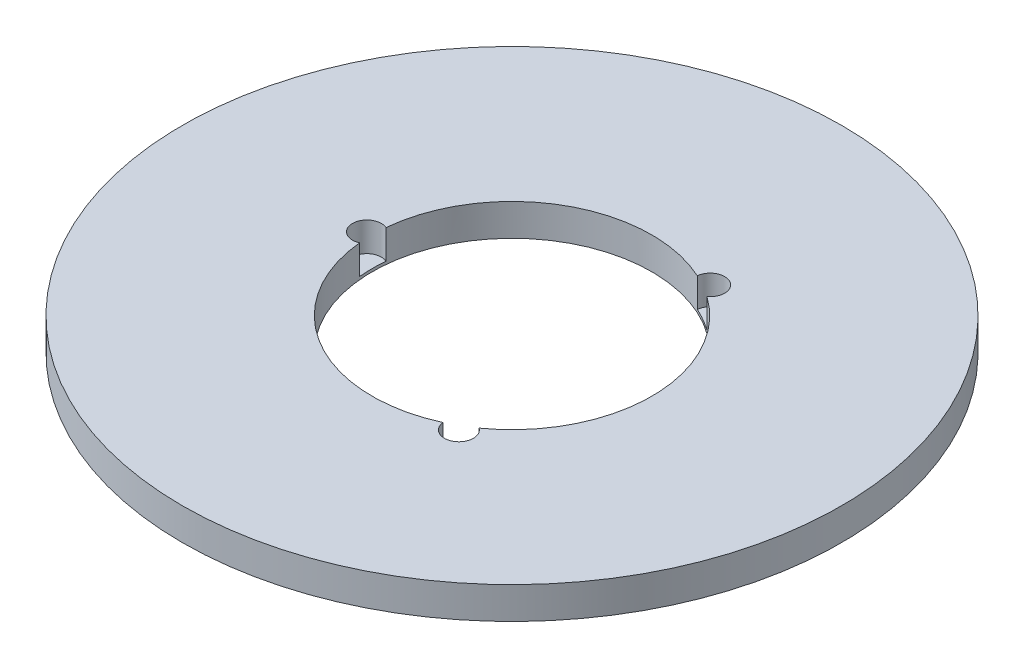
SolidWorks part; units mm, degrees
ref_plane "Front Plane" through (0, 0, 0) normal (0, 0, 1) x (1, 0, 0)
ref_plane "Top Plane" through (0, 0, 0) normal (0, 1, 0) x (1, 0, 0)
ref_plane "Right Plane" through (0, 0, 0) normal (1, 0, 0) x (0, 0, -1)
sketch "Sketch1" plane through (0, 0, 0) normal (0, 1, 0) x (1, 0, 0)
  circle A0 centre (0, 0) radius 82.5
  dimension "FLANGE_OD" = 165
extrude "Boss-Extrude1" add sketch "Sketch1" along normal blind 8
sketch "Sketch2" plane through (0, 0, 0) normal (0, 1, 0) x (1, 0, 0)
  circle A0 centre (0, 0) radius 35
  dimension "BORE_D" = 70
extrude "Cut-Extrude1" cut sketch "Sketch2" along normal through all
sketch "Sketch3" plane through (0, 8, 0) normal (0, 1, 0) x (1, 0, 0)
  circle A0 centre (0, 0) radius 36.3196 construction
  circle A1 centre (-36.3196, 0) radius 3.6217
  dimension "BOLT_D" = 7.2435
  dimension "BOLT_PCD" = 72.6393
extrude "Cut-Extrude2" cut sketch "Sketch3" against normal blind 7.3016
pattern_circular "CirPattern1" count 3 over 360 about axis through (0, 0, 0) along (0, 1, 0) of "Cut-Extrude2"
